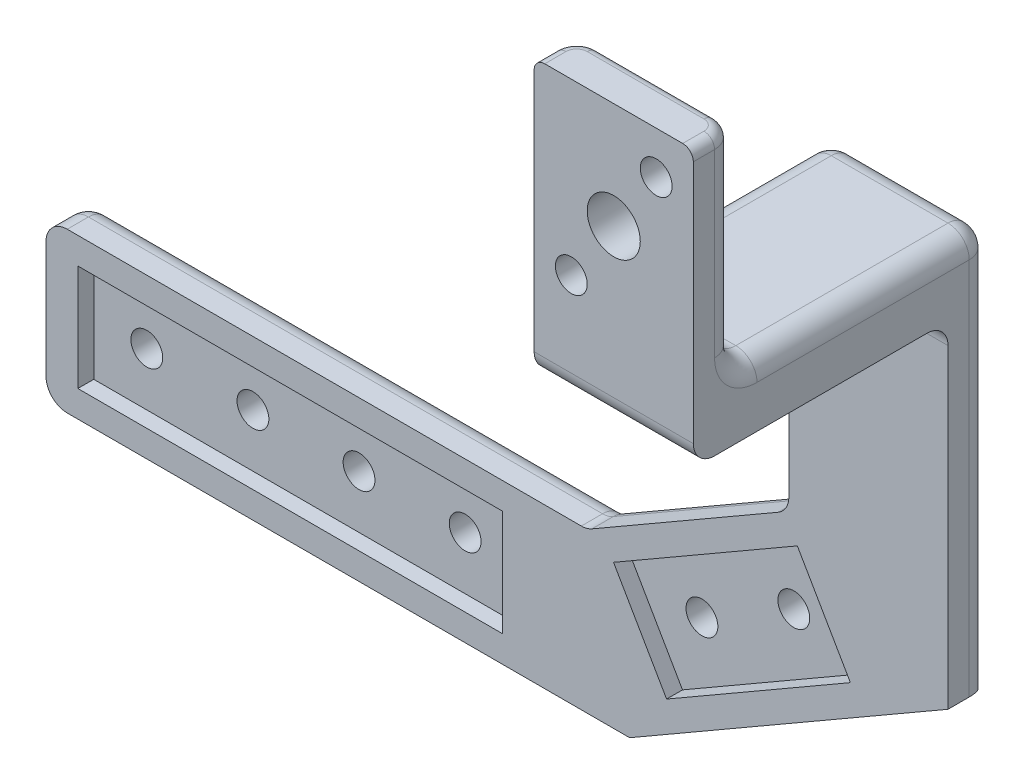
SolidWorks part; units mm, degrees
ref_plane "前视基准面" through (0, 0, 0) normal (0, 0, 1) x (1, 0, 0)
ref_plane "上视基准面" through (0, 0, 0) normal (0, 1, 0) x (1, 0, 0)
ref_plane "右视基准面" through (0, 0, 0) normal (1, 0, 0) x (0, 0, -1)
sketch "草图1" plane through (0, 0, 0) normal (0, 0, 1) x (1, 0, 0)
  line L0 (-7.5, 10) -> (-7.5, -16)
  line L3 (-7.5, 10) -> (7.5, 10)
  line L5 (0, 10) -> (0, -10) construction
  line L6 (-2.5, 0) -> (2.5, 0) construction
  line L9 (-7.5, -16) -> (7.5, -16)
  line L11 (7.5, 10) -> (7.5, -16)
  circle A0 centre (0, 0) radius 2.5
  circle A1 centre (4, 6) radius 1.5
  circle A2 centre (-4, -6) radius 1.5
  point P0 (0, 0)
  dimension "D3" = 5
  dimension "D4" = 3
  dimension "D5" = 3
  dimension "D1" = 26
  dimension "D2" = 15
  dimension "D6" = 4
  dimension "D7" = 4
  dimension "D8" = 6
  dimension "D9" = 6
  dimension "D10" = 15
  dimension "D11" = 10
extrude "凸台-拉伸1" add sketch "草图1" along normal blind 4
sketch "草图3" plane through (0, 0, 0) normal (0, 0, -1) x (-1, 0, 0)
  line L0 (7.5, 10) -> (7.5, -16) construction
  line L1 (-7.5, -16) -> (7.5, -16)
  line L2 (-7.5, -16) -> (-7.5, -10)
  line L3 (-7.5, -10) -> (7.5, -10)
  line L4 (7.5, -16) -> (7.5, -10)
  line L5 (-7.5, -16) -> (-7.5, 10) construction
  dimension "D1" = 6
extrude "凸台-拉伸2" add sketch "草图3" along normal blind 20
sketch "草图8" plane through (0, 0, -20) normal (0, 0, -1) x (-1, 0, 0)
  line L0 (-7.5, -16) -> (-7.5, -47.6795)
  line L1 (7.5, -16) -> (7.5, -39.0192)
  line L2 (7.5, -39.0192) -> (26.5192, -50)
  line L3 (26.5192, -50) -> (77.5, -50)
  line L4 (-7.5, -10) -> (-7.5, -16)
  line L5 (-7.5, -16) -> (7.5, -16)
  line L6 (7.5, -16) -> (7.5, -10)
  line L7 (7.5, -10) -> (-7.5, -10)
  line L8 (-7.5, -10) -> (-7.5, -16)
  line L10 (7.5, -16) -> (7.5, -10)
  line L11 (7.5, -10) -> (-7.5, -10)
  line L12 (77.5, -50) -> (77.5, -65)
  line L13 (77.5, -65) -> (22.5, -65)
  line L18 (-7.5, -47.6795) -> (22.5, -65)
  dimension "D2" = 55
  dimension "D3" = 150
  dimension "D4" = 85
  dimension "D5" = 15
  dimension "D6" = 55
  dimension "D7" = 150
  dimension "D8" = 15
  dimension "D9" = 15
  dimension "D1" = 0
extrude "凸台-拉伸3" add sketch "草图8" along normal blind 4
sketch "草图9" plane through (0, 0, -20) normal (0, 0, 1) x (1, 0, 0)
  line L0 (-77.5, -50) -> (-26.5192, -50) construction
  line L1 (-74.5, -52.5) -> (-34.5, -52.5)
  line L2 (-74.5, -52.5) -> (-74.5, -62.5)
  line L3 (-74.5, -62.5) -> (-34.5, -62.5)
  line L4 (-34.5, -52.5) -> (-34.5, -62.5)
  line L5 (-22.5, -65) -> (-77.5, -65) construction
  line L6 (-77.5, -65) -> (-77.5, -50) construction
  dimension "D1" = 40
  dimension "D2" = 2.5
  dimension "D3" = 2.5
  dimension "D4" = 3
extrude "切除-拉伸1" cut sketch "草图9" against normal blind 1.5
sketch "草图10" plane through (0, 0, -21.5) normal (0, 0, 1) x (1, 0, 0)
  line L0 (-74.5, -52.5) -> (-74.5, -62.5) construction
  line L1 (-34.5, -52.5) -> (-74.5, -52.5) construction
  circle A0 centre (-69.5, -57.5) radius 1.5
  circle A1 centre (-59.5, -57.5) radius 1.5
  circle A2 centre (-49.5, -57.5) radius 1.5
  circle A3 centre (-39.5, -57.5) radius 1.5
  dimension "D1" = 5
  dimension "D3" = 3
  dimension "D2" = 5
  dimension "D4" = 4
extrude "切除-拉伸2" cut sketch "草图10" against normal blind 4
sketch "草图11" plane through (0, 0, -20) normal (0, 0, 1) x (1, 0, 0)
  line L5 (-6.6987, -41.4434) -> (-24.0192, -51.4434)
  line L6 (-24.0192, -51.4434) -> (-19.0192, -60.1036)
  line L7 (-19.0192, -60.1036) -> (-1.6987, -50.1036)
  line L8 (-1.6987, -50.1036) -> (-6.6987, -41.4434)
  line L10 (-26.5192, -50) -> (-7.5, -39.0192) construction
  dimension "D1" = 20
  dimension "D4" = 90
  dimension "D5" = 90
  dimension "D6" = 2.5
  dimension "D7" = 10
  dimension "D10" = 2.5
extrude "切除-拉伸3" cut sketch "草图11" against normal blind 1.5
sketch "草图12" plane through (0, 0, -21.5) normal (0, 0, 1) x (1, 0, 0)
  line L0 (-1.6987, -50.1036) -> (-6.6987, -41.4434) construction
  line L1 (-24.0192, -51.4434) -> (-19.0192, -60.1036) construction
  line L2 (-6.6987, -41.4434) -> (-24.0192, -51.4434) construction
  circle A0 centre (-17.1891, -53.2735) radius 1.5
  circle A1 centre (-8.5289, -48.2735) radius 1.5
  dimension "D1" = 3
  dimension "D2" = 3
  dimension "D3" = 5
  dimension "D4" = 5
  dimension "D5" = 5
  dimension "D6" = 5
extrude "切除-拉伸4" cut sketch "草图12" against normal blind 10
fillet "圆角1" radius 2 17 edges at (-7.5, -24.5096, -24) (-17.0096, -44.5096, -24) (-7.5, -10, -12) (7.5, -10, -12) (7.5, -28.8397, -24) (-50, -65, -24) (-77.5, -65, -22) (-77.5, -50, -22) (-77.5, -57.5, -24) (-52.0096, -50, -24) (-26.5192, -50, -22) (-7.5, -39.0192, -22) (0, -16, -20) (0, -10, -24) (0, -10, 0) (7.5, 0, 0) (-7.5, 0, 0)
fillet "圆角2" radius 2 1 edges at (0, -16, 4)
fillet "圆角3" radius 1 5 edges at (7.5, 10, 3) (6.9142, 10, 0.5858) (-7.5, 10, 3) (-6.9142, 10, 0.5858) (0, 10, 0)
